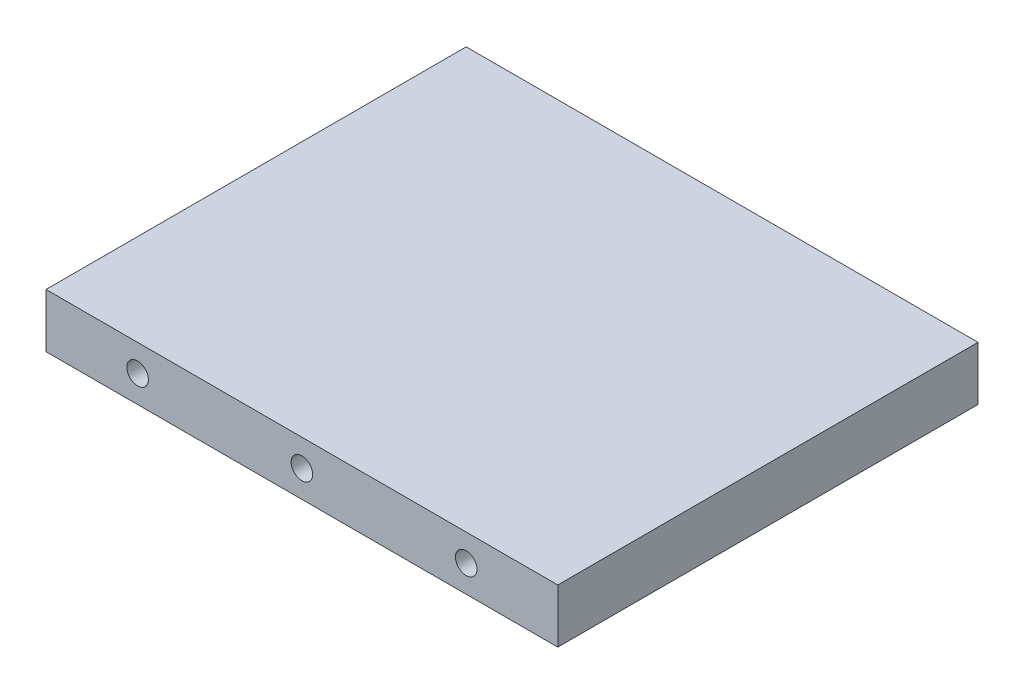
SolidWorks part; units mm, degrees
ref_plane "Piano frontale" through (0, 0, 0) normal (0, 0, 1) x (1, 0, 0)
ref_plane "Piano superiore" through (0, 0, 0) normal (0, 1, 0) x (1, 0, 0)
ref_plane "Piano destro" through (0, 0, 0) normal (1, 0, 0) x (0, 0, -1)
sketch "Schizzo2" plane through (0, 0, 0) normal (0, 0, 1) x (1, 0, 0)
  line L1 (0, 0) -> (95, 0)
  line L2 (0, 0) -> (0, 10)
  line L3 (0, 10) -> (95, 10)
  line L4 (95, 0) -> (95, 10)
  dimension "D1" = 10
  dimension "D2" = 95
extrude "Estrusione-Estrusione1" add sketch "Schizzo2" against normal blind 78
sketch "Schizzo3" plane through (0, 0, 0) normal (0, 0, 1) x (1, 0, 0)
  line L0 (0, 5) -> (95, 5) construction
  line L1 (0, 10) -> (0, 0) construction
  line L2 (95, 0) -> (95, 10) construction
  line L3 (47.5, 10) -> (47.5, 0) construction
  line L4 (95, 10) -> (0, 10) construction
  line L5 (0, 0) -> (95, 0) construction
  circle A0 centre (17, 5) radius 2
  circle A1 centre (47.5, 5) radius 2
  circle A2 centre (78, 5) radius 2
  dimension "D2" = 4
  dimension "D3" = 4
  dimension "D1" = 30.5
extrude "Taglio-Estrusione1" cut sketch "Schizzo3" against normal blind 15
sketch "Schizzo4" plane through (0, 0, -78) normal (0, 0, -1) x (-1, 0, 0)
  line L0 (-95, 5) -> (0, 5) construction
  line L1 (-95, 0) -> (-95, 10) construction
  line L2 (0, 10) -> (0, 0) construction
  line L3 (-47.5, 10) -> (-47.5, 0) construction
  line L4 (-95, 10) -> (0, 10) construction
  line L5 (0, 0) -> (-95, 0) construction
  circle A0 centre (-78, 5) radius 2
  circle A1 centre (-47.5, 5) radius 2
  circle A2 centre (-17, 5) radius 2
  dimension "D2" = 4
  dimension "D3" = 4
  dimension "D1" = 30.5
extrude "Taglio-Estrusione2" cut sketch "Schizzo4" against normal blind 15
